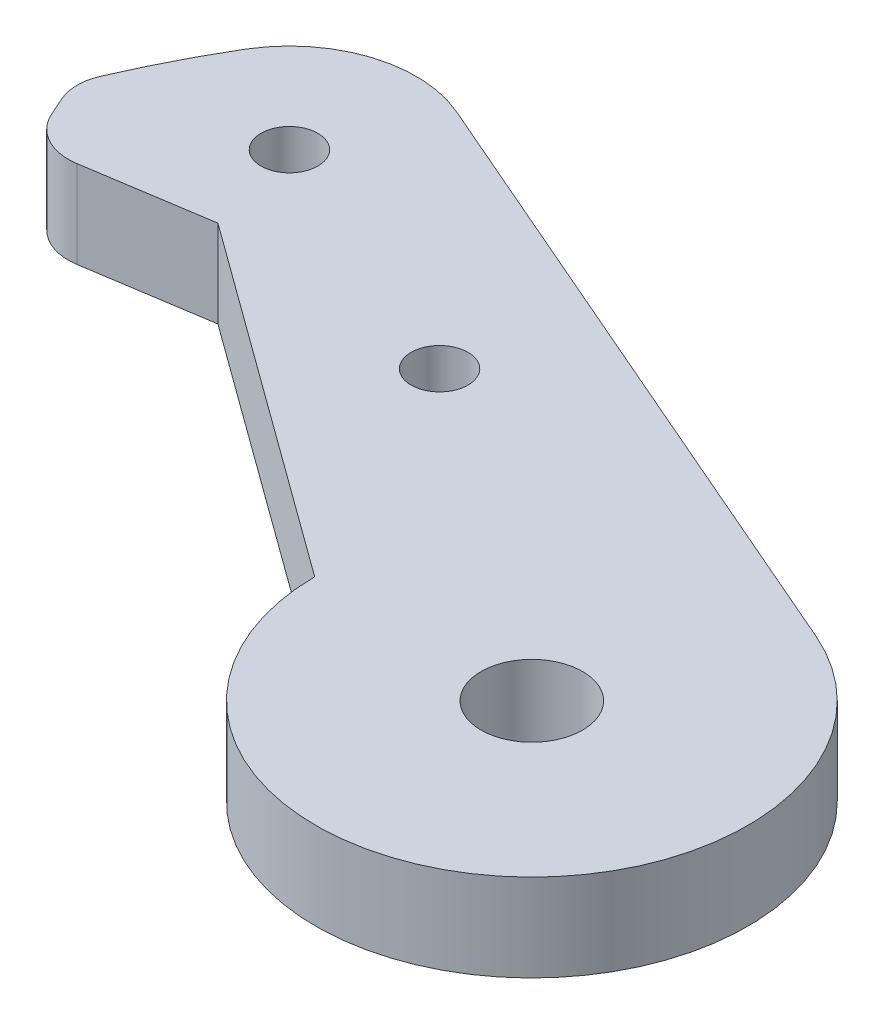
SolidWorks part; units mm, degrees
ref_plane "Front" through (0, 0, 0) normal (0, 0, 1) x (1, 0, 0)
ref_plane "Top" through (0, 0, 0) normal (0, 1, 0) x (1, 0, 0)
ref_plane "Right" through (0, 0, 0) normal (1, 0, 0) x (0, 0, -1)
ref_axis "side-side" through (80.9, 0, 0) along (-1, 0, 0)
ref_axis "up-down" through (0, 50, 0) along (0, -1, 0)
ref_axis "front-back" through (0, 0, -80.9) along (0, 0, 1)
sketch "Sketch1" plane through (0, 0, 0) normal (0, 1, 0) x (1, 0, 0)
  line L0 (-37.5348, 16.5677) -> (-37.4529, 17.3438) construction
  line L1 (-38.7702, 16.758) -> (-42.4833, 15.1067) construction
  line L2 (-35.6712, 16.0482) -> (-13.4998, -0.0747)
  line L3 (-46.7735, 16.7556) -> (-47.2827, 17.9005)
  line L5 (-34.2596, 29.5434) -> (5.3636, 12.3888)
  line L6 (-36.2869, 16.4959) -> (-38.7702, 16.758) construction
  line L8 (-43.3061, 14.8646) -> (-35.6712, 16.0482)
  arc A0 (-43.3061, 14.8646) -> (-46.7735, 16.7556) centre (-43.8039, 18.0763) cw
  arc A1 (-47.2983, 20.3029) -> (-44.2347, 26.3178) centre (0, 0) cw
  arc A2 (-47.2983, 20.3029) -> (-47.2827, 17.9005) centre (-44.5415, 19.1196) ccw
  arc A3 (-34.2596, 29.5434) -> (-44.2347, 26.3178) centre (-37.4133, 22.2593) ccw
  arc A4 (-38.7702, 16.758) -> (-36.2869, 16.4959) centre (-37.5348, 16.5677) cw construction
  arc A5 (-13.4998, -0.0747) -> (5.3636, 12.3888) centre (0, 0) ccw
  arc A6 (-35.6712, 16.0482) -> (-42.4833, 15.1067) centre (-37.4471, 3.7822) ccw construction
  arc A7 (-44.8796, 24.9532) -> (-31.4102, 17.0663) centre (-37.4133, 22.2593) ccw construction
  circle A10 centre (8, 0) radius 1.75 construction
  circle A11 centre (0, -8) radius 1.75 construction
  circle A12 centre (-8, 0) radius 1.75 construction
  circle A13 centre (0, 8) radius 1.75 construction
  circle A14 centre (-20.8625, 15.0937) radius 1.778
  circle A15 centre (0, 0) radius 3.175
  circle A16 centre (-20.8625, 15.0937) radius 7.9375 construction
  circle A18 centre (-37.4133, 22.2593) radius 1.778
  point P0 (-37.4529, 17.3438)
  point P11 (-45.4529, 13.786)
  point P21 (-35.6712, 16.0482)
  point P23 (-36.4799, 16.6363)
  dimension "D2" = 3
  dimension "D4" = 13.5
  dimension "D5" = 1
  dimension "D8" = 3.25
  dimension "D9" = 0.7804
  dimension "D7" = 1.25
  dimension "D11" = 15.875
  dimension "D13" = 6.35
  dimension "D14" = 3.556
  dimension "D1" = 8.7554
  dimension "D3" = 8
  dimension "D6" = 120
  dimension "D12" = 25.75
extrude "Boss-Extrude1" add sketch "Sketch1" along normal blind 5.461
